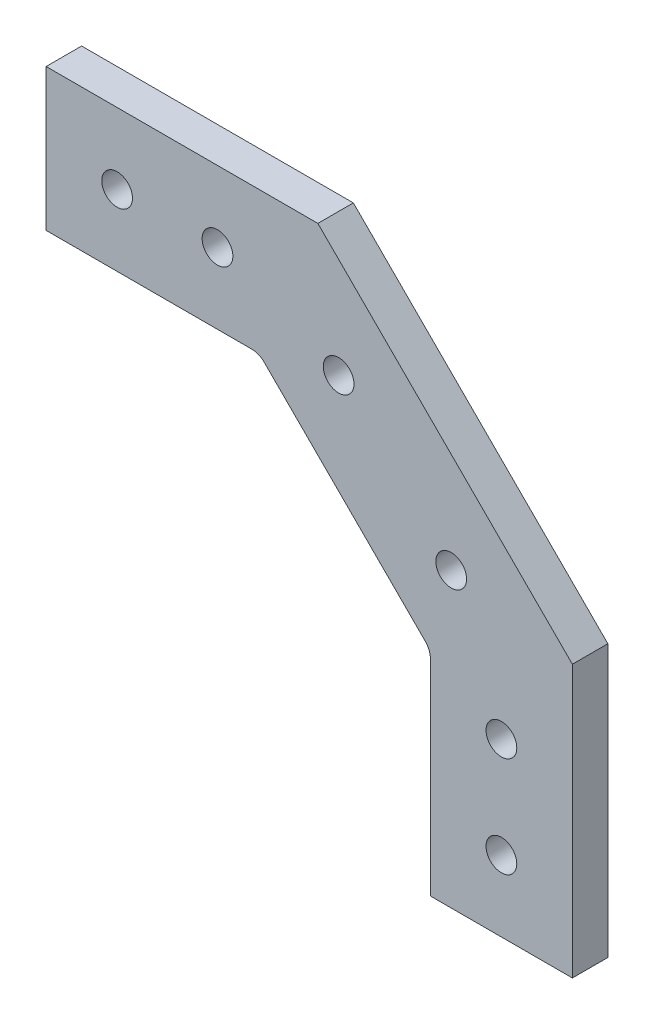
SolidWorks part; units mm, degrees
material "6061-T6 (SS)"
ref_plane "Front" through (0, 0, 0) normal (0, 0, 1) x (1, 0, 0)
ref_plane "Top" through (0, 0, 0) normal (0, 1, 0) x (1, 0, 0)
ref_plane "Right" through (0, 0, 0) normal (1, 0, 0) x (0, 0, -1)
sketch "Sketch4" plane through (-304.8, 0, 0) normal (0, 0, 1) x (1, 0, 0)
  line L0 (317.5, 63.5) -> (317.5, 0)
  line L2 (317.5, 63.5) -> (279.4, 101.6)
  line L4 (279.4, 101.6) -> (-279.4, 101.6)
  line L5 (317.5, 0) -> (-317.5, 0) construction
  line L6 (-279.4, 101.6) -> (-317.5, 63.5)
  line L7 (-317.5, 63.5) -> (-317.5, -25.4)
sketch "Sketch1" plane through (0, 0, 0) normal (0, 0, 1) x (1, 0, 0)
  line L0 (0, 38.1) -> (0, 58.2395)
  line L6 (0, 58.2395) -> (-30.6605, 88.9)
  line L7 (-30.6605, 88.9) -> (-68.7605, 88.9)
  line L8 (-68.7605, 88.9) -> (-68.7605, 114.3)
  line L9 (-68.7605, 114.3) -> (-20.1395, 114.3)
  line L10 (-20.1395, 114.3) -> (25.4, 68.7605)
  line L11 (25.4, 68.7605) -> (25.4, 63.5)
  line L12 (0, 38.1) -> (0, 0) construction
  line L13 (12.7, 63.5) -> (-25.4, 101.6) construction
  line L14 (-25.4, 101.6) -> (-584.2, 101.6) construction
  line L15 (25.4, 63.5) -> (0, 63.5) construction
  line L16 (0, 63.5) -> (0, 58.2395) construction
  line L17 (25.4, 38.1) -> (25.4, 20.1395)
  line L18 (25.4, 20.1395) -> (0, 20.1395)
  line L19 (0, 20.1395) -> (0, 38.1)
  line L20 (25.4, 38.1) -> (0, 38.1) construction
  line L21 (25.4, 63.5) -> (25.4, 38.1)
  dimension "D3" = 38.1
  dimension "D5" = 12.7
  dimension "D6" = 12.7
  dimension "D7" = 12.7
  dimension "D8" = 12.7
  dimension "D9" = 38.1
extrude "Boss-Extrude1" add sketch "Sketch1" along normal blind 6.35
fillet "Fillet1" radius 3.175 2 edges at (-30.6605, 88.9, 3.175) (0, 58.2395, 3.175)
hole_wizard "M5 Clearance Hole1" positions "Sketch2" profile "Sketch3" hole size "M5" standard "ANSI Metric"
sketch "Sketch2" plane through (0, 0, 6.35) normal (0, 0, 1) x (1, 0, 0)
  line L14 (-68.7605, 114.3) -> (-56.0605, 101.6) construction
  line L15 (-56.0605, 101.6) -> (-68.7605, 88.9) construction
  line L17 (-56.0605, 101.6) -> (-38.1, 101.6) construction
  line L19 (-16.4197, 92.6197) -> (3.7197, 72.4803) construction
  line L21 (25.4, 68.7605) -> (-20.1395, 114.3) construction
  line L22 (25.4, 20.1395) -> (12.7, 32.8395) construction
  line L23 (12.7, 32.8395) -> (0, 20.1395) construction
  line L25 (12.7, 32.8395) -> (12.7, 50.8) construction
  point P0 (12.7, 50.8)
  point P44 (3.7197, 72.4803)
  point P46 (-16.4197, 92.6197)
  point P48 (-38.1, 101.6)
  point P50 (-56.0605, 101.6)
  point P87 (12.7, 32.8395)
  dimension "D1" = 12.7
  dimension "D2" = 12.7
  dimension "D3" = 12.7
  dimension "D4" = 12.7
sketch "Sketch3" plane through (12.7, 50.8, 6.35) normal (1, 0, 0) x (0, -1, 0)
  line L0 (0, 0) -> (0, 20.4024)
  line L1 (0, 20.4024) -> (2.75, 18.75)
  line L2 (2.75, 18.75) -> (2.75, 0)
  line L5 (2.75, 0) -> (0, 0)
  line L10 (0, 20.4024) -> (-2.75, 18.75) construction
  line L11 (0, -6.35) -> (0, 107.95) construction
  dimension "Hole Dia." = 5.5
  dimension "Hole Depth" = 18.75
  dimension "Drill Angle" = 118
